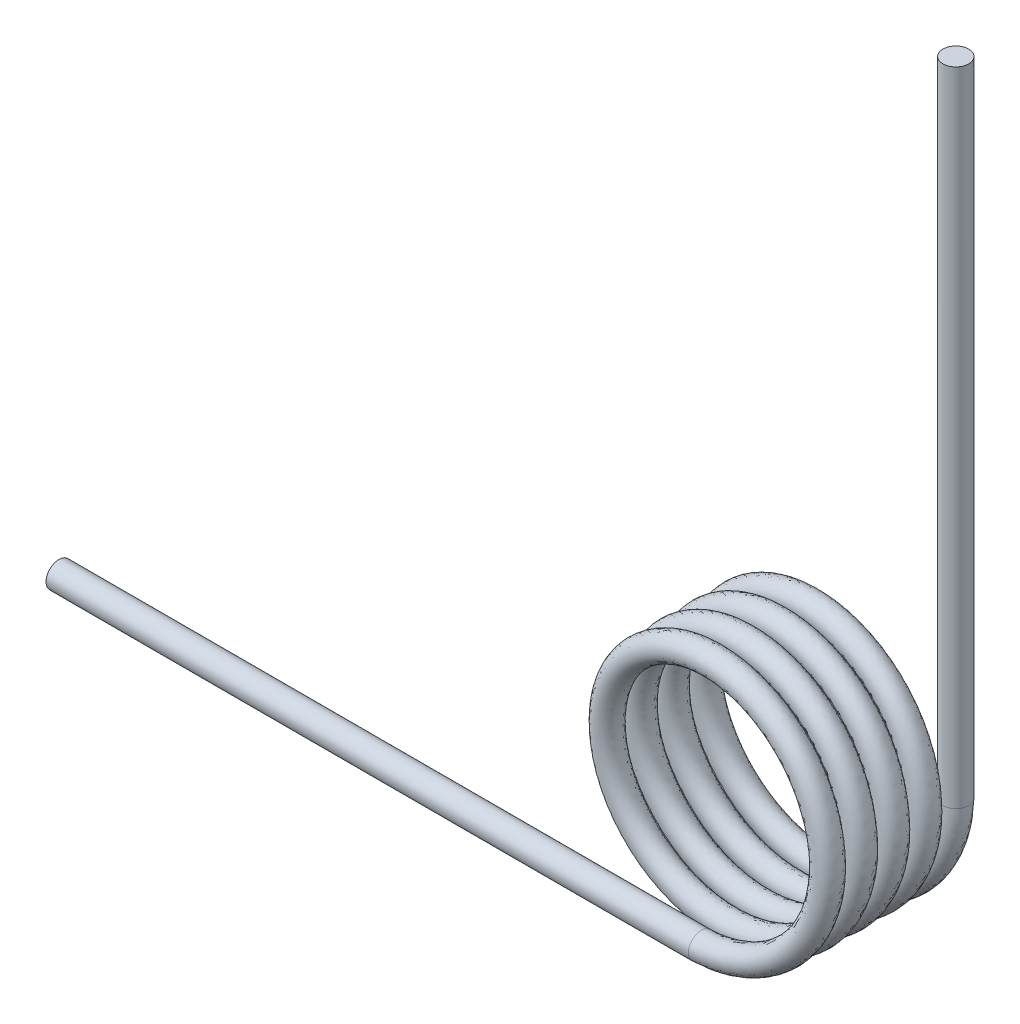
SolidWorks part; units mm, degrees
ref_plane "Alzado" through (0, 0, 0) normal (0, 0, 1) x (1, 0, 0)
ref_plane "Planta" through (0, 0, 0) normal (0, 1, 0) x (1, 0, 0)
ref_plane "Vista lateral" through (0, 0, 0) normal (1, 0, 0) x (0, 0, -1)
sketch "Croquis1" plane through (0, 0, 0) normal (0, 0, 1) x (1, 0, 0)
  circle A0 centre (0, 0) radius 3.675
  dimension "D1" = 7.35
curve "Hélice/Espiral1" pitch 1 height 4.25 turns 4.25
ref_plane "Plano4" through (0, 0, 0) normal (1, 0, 0) x (0, 0, -1)
sketch "Croquis7" plane through (0, 0, 0) normal (1, 0, 0) x (0, 0, -1)
  circle A0 centre (-4.25, -3.675) radius 0.4
  point P2 (0, 0)
  dimension "D1" = 0.8
sweep "Barrer2" add profiles "Croquis7" path "Hélice/Espiral1"
sketch "Croquis8" plane through (0, 0, 0) normal (-1, 0, 0) x (0, 0, 1)
  circle A0 centre (4.25, -3.675) radius 0.4
extrude "Saliente-Extruir1" add sketch "Croquis8" along normal blind 20
sketch "Croquis9" plane through (0, 0, 0) normal (0, 1, 0) x (1, 0, 0)
  circle A0 centre (3.675, 0) radius 0.4
extrude "Saliente-Extruir2" add sketch "Croquis9" along normal blind 20
